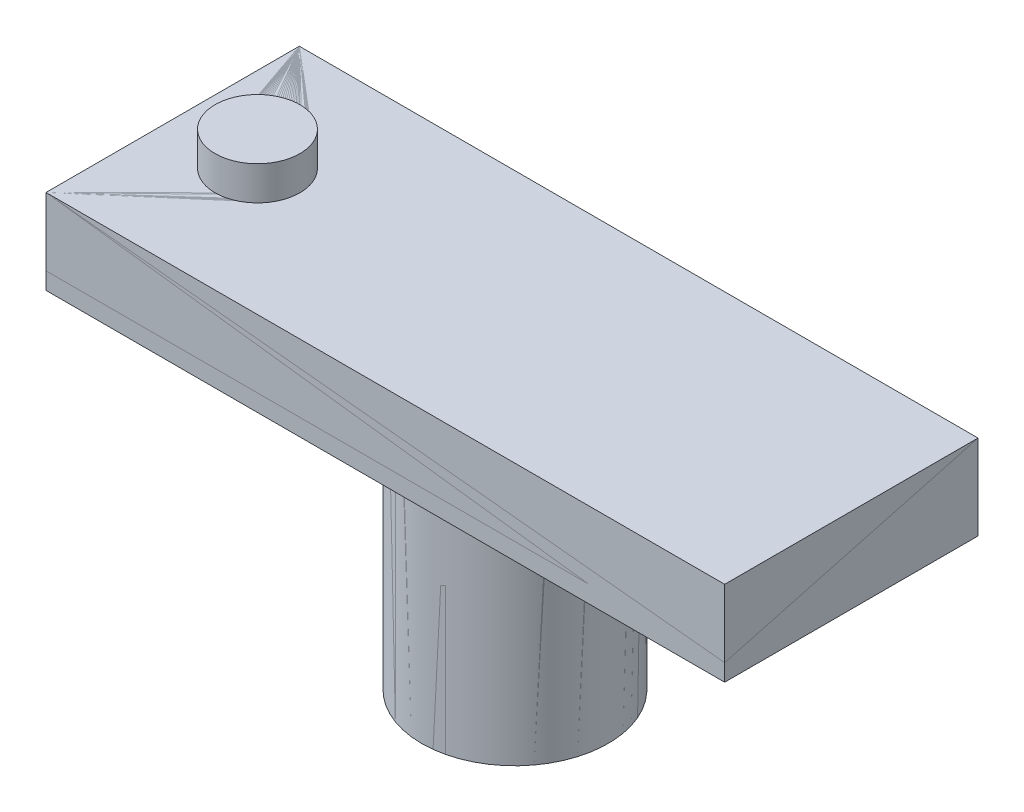
SolidWorks part; units mm, degrees
ref_plane "Front Plane" through (0, 0, 0) normal (0, 0, 1) x (1, 0, 0)
ref_plane "Top Plane" through (0, 0, 0) normal (0, 1, 0) x (1, 0, 0)
ref_plane "Right Plane" through (0, 0, 0) normal (1, 0, 0) x (0, 0, -1)
sketch "Sketch1" plane through (0, 0, 0) normal (0, 1, 0) x (1, 0, 0)
  circle A0 centre (0.1961, -0.0239) radius 5.5
  circle A1 centre (0, 0) radius 4
extrude "Boss-Extrude1" add sketch "Sketch1" along normal blind 15
sketch "Sketch3" plane through (0, 15, 0) normal (0, 1, 0) x (1, 0, 0)
  line L0 (-2.2135, 6.1896) -> (2.2135, 6.1896)
  line L1 (-20, 7.4654) -> (20, 7.4654)
  line L2 (-20, 7.4654) -> (-20, -7.4654)
  line L3 (-20, -7.4654) -> (20, -7.4654)
  line L4 (20, 7.4654) -> (20, -7.4654)
  line L5 (-2.2135, -6.1896) -> (2.2135, -6.1896)
  circle A0 centre (-15, 0) radius 2.5
  circle A1 centre (15, 0) radius 2.5
  spline S0 degree 2 poles (0, 7.4654) (-9.9271, 1.1939) (-20, 4.7073) knots 0 0 0 1 1 1
  spline S1 degree 2 poles (0, -7.4654) (-9.9271, -1.1939) (-20, -4.7073) knots 0 0 0 1 1 1
  spline S2 degree 2 poles (-15, 3.5651) (-25, 0) (-15, -3.5651) knots 0 0 0 1 1 1
  spline S3 degree 2 poles (0, 7.4654) (9.9271, 1.1939) (20, 4.7073) knots 0 0 0 1 1 1
  spline S4 degree 2 poles (0, -7.4654) (9.9271, -1.1939) (20, -4.7073) knots 0 0 0 1 1 1
  spline S5 degree 2 poles (15, 3.5651) (25, 0) (15, -3.5651) knots 0 0 0 1 1 1
extrude "Boss-Extrude2" add sketch "Sketch3" along normal blind 4 and the other way blind 1 contours L4 L3 L2 L1
extrude "Cut-Extrude1" cut sketch "Sketch3<4>" along normal blind 9 and the other way blind 10 contours A1
sketch "Sketch3<4>" plane through (0, 15, 0) normal (0, 1, 0) x (1, 0, 0) same geometry as "Sketch3"
extrude "Cut-Extrude6" cut sketch "Sketch3<6>" against normal blind 12 and the other way blind 14 contours A0
sketch "Sketch3<6>" plane through (0, 15, 0) normal (0, 1, 0) x (1, 0, 0) same geometry as "Sketch3"
extrude "Boss-Extrude3" add sketch "Sketch1<2>" along normal blind 15 separate body
sketch "Sketch1<2>" plane through (0, 0, 0) normal (0, 1, 0) x (1, 0, 0) same geometry as "Sketch1"
extrude "Boss-Extrude4" add sketch "Sketch3<15>" along normal blind 4 contours L1 L4 L3 L2
sketch "Sketch3<15>" plane through (0, 15, 0) normal (0, 1, 0) x (1, 0, 0) same geometry as "Sketch3"
extrude "Boss-Extrude6" add sketch "Sketch3<18>" along normal blind 6 and the other way blind 3 contours A0
sketch "Sketch3<18>" plane through (0, 15, 0) normal (0, 1, 0) x (1, 0, 0) same geometry as "Sketch3"
